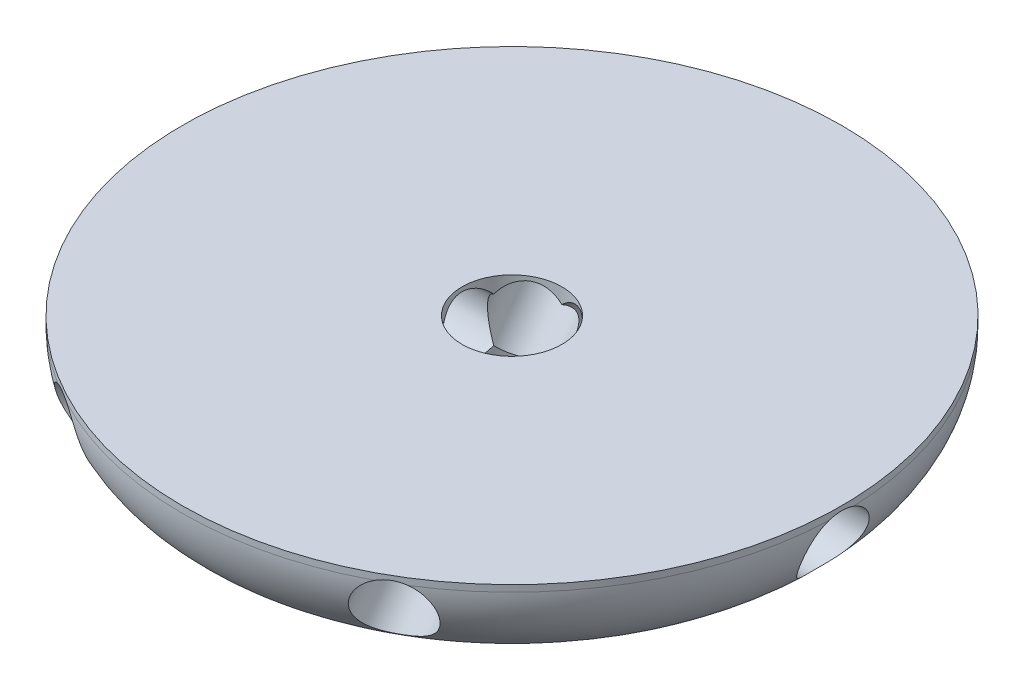
SolidWorks part; units mm, degrees
ref_plane "前视基准面" through (0, 0, 0) normal (0, 0, 1) x (1, 0, 0)
ref_plane "上视基准面" through (0, 0, 0) normal (0, 1, 0) x (1, 0, 0)
ref_plane "右视基准面" through (0, 0, 0) normal (1, 0, 0) x (0, 0, -1)
sketch "草图1" plane through (0, 0, 0) normal (0, 1, 0) x (1, 0, 0)
  circle A0 centre (0, 0) radius 50
extrude "凸台-拉伸1" add sketch "草图1" along normal blind 7 and the other way blind 7
sketch "草图3" plane through (0, 0, 0) normal (1, 0, 0) x (0, 0, -1)
  circle A0 centre (0, 1.2773) radius 5.075
  dimension "D1" = 10.15
extrude "切除-拉伸1" cut sketch "草图3" against normal through all
pattern_circular "阵列(圆周)1" count 6 over 360 about axis through (0, 7, 0) along (0, 1, 0) of "切除-拉伸1"
fillet "圆角1" radius 13 1 edges at (0, -7, 50) type face fillet first side face at (-20.5942, 2.4152, 45.5618) second side face at (0, -7, 50)
sketch "草图4" plane through (0, 7, 0) normal (0, 1, 0) x (1, 0, 0)
  circle A0 centre (0, 0) radius 7.575
  dimension "D1" = 15.15
extrude "切除-拉伸2" cut sketch "草图4" against normal through all
